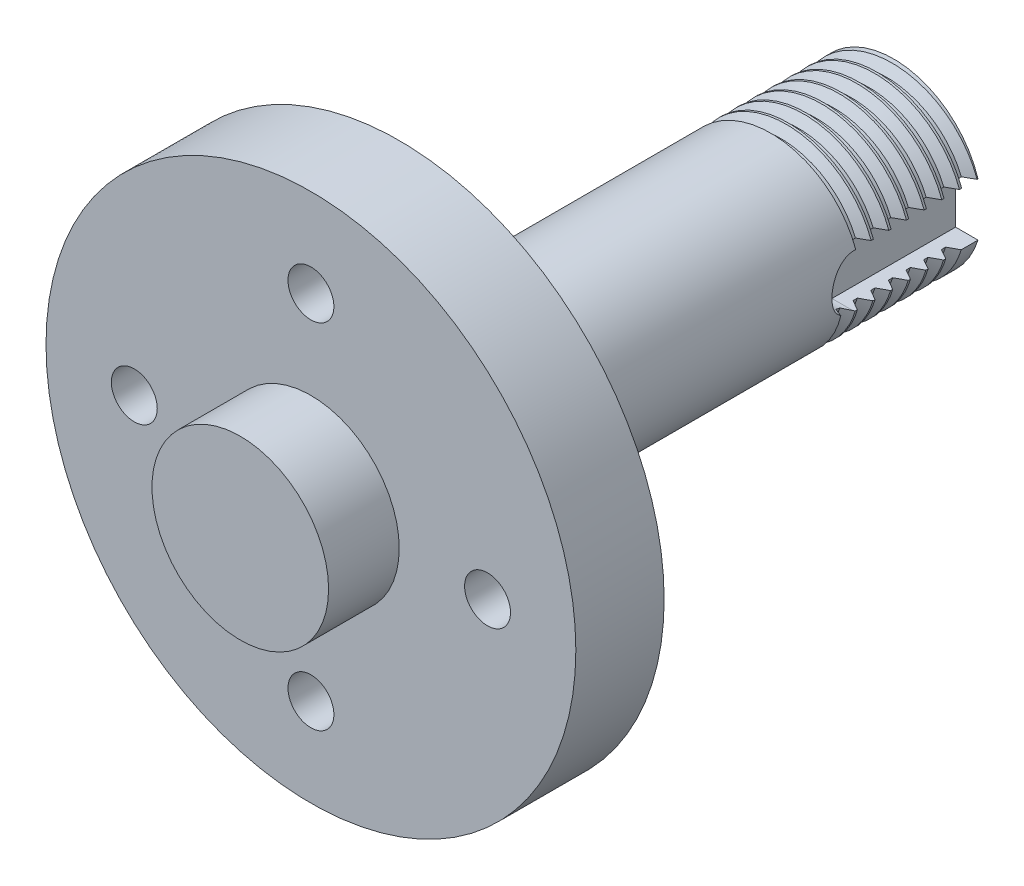
SolidWorks part; units mm, degrees
ref_plane "Front Plane" through (0, 0, 0) normal (0, 0, 1) x (1, 0, 0)
ref_plane "Top Plane" through (0, 0, 0) normal (0, 1, 0) x (1, 0, 0)
ref_plane "Right Plane" through (0, 0, 0) normal (1, 0, 0) x (0, 0, -1)
sketch "Sketch1" plane through (0, 0, 0) normal (0, 0, 1) x (1, 0, 0)
  circle A0 centre (0, 0) radius 5
  dimension "D1" = 10
extrude "Boss-Extrude1" add sketch "Sketch1" along normal blind 24
sketch "Sketch2" plane through (0, 0, 24) normal (0, 0, 1) x (1, 0, 0)
  circle A0 centre (0, 0) radius 6
extrude "Boss-Extrude2" add sketch "Sketch2" along normal blind 4
sketch "Sketch3" plane through (0, 0, 28) normal (0, 0, 1) x (1, 0, 0)
  circle A0 centre (0, 0) radius 15
extrude "Boss-Extrude3" add sketch "Sketch3" along normal blind 5
sketch "Sketch4" plane through (0, 0, 33) normal (0, 0, 1) x (1, 0, 0)
  circle A0 centre (0, 0) radius 5
extrude "Boss-Extrude4" add sketch "Sketch4" along normal blind 4
sketch "Sketch5" plane through (0, 0, 33) normal (0, 0, 1) x (1, 0, 0)
  point P0 (0, 10)
  point P2 (10, 0)
  point P4 (0, -10)
  point P6 (-10, 0)
hole_wizard "Tap Drill for M3x0.5 Tap1" positions "Sketch5" profile "Sketch6" hole size "M3x0.5" standard "JIS" end condition through all
sketch "Sketch6" plane through (0, 10, 33) normal (1, 0, 0) x (0, -1, 0)
  line L0 (0, 0) -> (0, 33)
  line L1 (0, 33) -> (1.3, 33)
  line L2 (1.3, 33) -> (1.3, 0)
  line L5 (1.3, 0) -> (0, 0)
  line L11 (0, -6.35) -> (0, 107.95) construction
  dimension "Thru Hole Dia." = 2.6
  dimension "Thru Hole Depth" = 33
sketch "Sketch7" plane through (0, 0, 0) normal (0, 0, -1) x (-1, 0, 0)
  line L1 (-5, -1.5) -> (-3.5, -1.5)
  line L2 (-5, -1.5) -> (-5, 1.5)
  line L3 (-5, 1.5) -> (-3.5, 1.5)
  line L4 (-3.5, -1.5) -> (-3.5, 1.5)
  line L5 (-5, -1.5) -> (-3.5, 1.5) construction
  line L6 (-5, 1.5) -> (-3.5, -1.5) construction
  point P0 (-5, 0)
extrude "Cut-Extrude5" cut sketch "Sketch7" against normal blind 7
sketch "Sketch8" plane through (3.5, 0, 0) normal (1, 0, 0) x (0, 0, -1)
  circle A0 centre (-7, 0) radius 1.5
extrude "Cut-Extrude6" cut sketch "Sketch8" against normal blind 1 and the other way through all
sketch "Sketch9" plane through (2.5, 0, 0) normal (1, 0, 0) x (0, 0, -1)
  circle A0 centre (-7, 0) radius 1.5
extrude "Boss-Extrude5" add sketch "Sketch9" along normal blind 1
thread "Thread1" pitch 1 method cut profile "Thread Profile1" start angle 0, offset 0, length 7, pitch 1, diameter 10
ref_plane "Plane2" through (5, 0, 0) normal (0, -1, 0) x (1, 0, 0)
sketch "Thread Profile1" plane through (5, 0, 0) normal (0, -1, 0) x (1, 0, 0)
  line L0 (0, 0) -> (0, 1) construction
  line L11 (0, 0) -> (0, 0.875)
  line L12 (0, 0.875) -> (-0.5413, 0.5625)
  line L13 (-0.5413, 0.5625) -> (-0.5413, 0.3125)
  line L15 (-0.5413, 0.3125) -> (0, 0)
  line L17 (-0.5413, 0.4375) -> (0, 0.4375) construction
  point P2 (0, 0)
  dimension "Pitch" = 1
  dimension "Profile_Angle" = 60
  dimension "Profile_Land" = 0.25
  dimension "Profile_Height" = 0.5413
